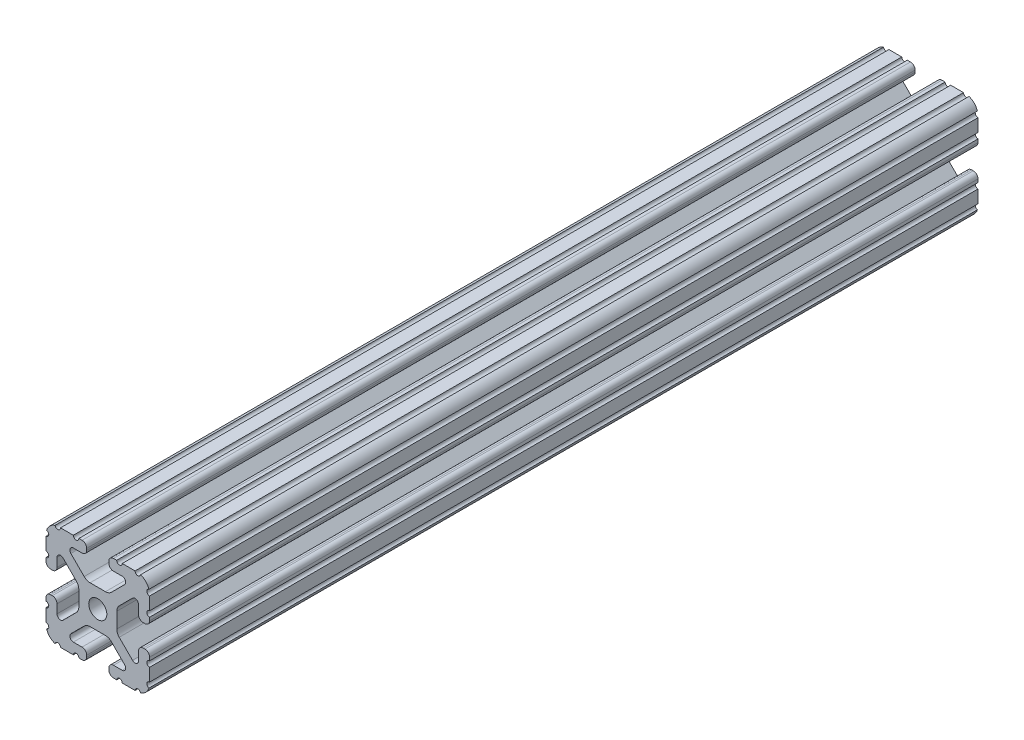
SolidWorks part; units mm, degrees
ref_plane "Front Plane" through (0, 0, 0) normal (0, 0, 1) x (1, 0, 0)
ref_plane "Top Plane" through (0, 0, 0) normal (0, 1, 0) x (1, 0, 0)
ref_plane "Right Plane" through (0, 0, 0) normal (1, 0, 0) x (0, 0, -1)
sketch "Sketch2" plane through (0, 0, 0) normal (0, 0, 1) x (1, 0, 0)
  line L0 (0, 19.05) -> (0, -19.05) construction
  line L1 (-19.05, 0) -> (19.05, 0) construction
  line L2 (4.064, -19.05) -> (19.05, -19.05)
  line L3 (19.05, -19.05) -> (19.05, -4.064)
  line L4 (4.064, -19.05) -> (4.064, -14.986)
  line L5 (4.064, -14.986) -> (12.1123, -14.986)
  line L6 (12.1123, -14.986) -> (4.1113, -6.985)
  line L7 (0, 0) -> (19.05, -19.05) construction
  line L8 (19.05, -4.064) -> (14.986, -4.064)
  line L9 (14.986, -4.064) -> (14.986, -12.1123)
  line L10 (14.986, -12.1123) -> (6.985, -4.1113)
  circle A0 centre (0, 0) radius 3.3274
  arc A1 (8.9963, -14.986) -> (9.909, -12.7826) centre (8.9963, -13.6953) ccw construction
  point P8 (0, -6.985)
  dimension "Center Hole Diameter" = 6.6548
  dimension "Rail Height" = 38.1
  dimension "Rail Width" = 38.1
  dimension "T-Slot Width" = 8.128
  dimension "Slot Inner Width" = 20.574
  dimension "Thickness" = 4.064
  dimension "Slot Depth" = 8.001
  dimension "D1" = 4.064
sketch "Sketch3" plane through (0, 0, 0) normal (1, 0, 0) x (0, 0, -1)
  line L0 (-152.4, -19.05) -> (152.4, -19.05) construction
  line L1 (-127, 0) -> (127, 0) construction
  dimension "Length" = 304.8
  dimension "D1" = 25.4
sketch "Sketch4" plane through (0, 0, 0) normal (0, 0, 1) x (1, 0, 0)
  line L0 (5.7912, -19.05) -> (14.3002, -19.05)
  line L1 (4.064, -19.05) -> (19.05, -19.05) construction
  line L2 (4.064, -19.05) -> (4.064, -14.986) construction
  line L3 (4.064, -14.986) -> (12.1123, -14.986) construction
  line L4 (4.064, -16.7132) -> (4.064, -17.3228)
  line L5 (5.7912, -14.986) -> (8.9963, -14.986)
  line L6 (0, -6.985) -> (2.833, -6.985)
  line L7 (12.1123, -14.986) -> (4.1113, -6.985) construction
  line L8 (5.0152, -7.8889) -> (9.909, -12.7826)
  line L9 (19.05, -19.05) -> (19.05, -4.064) construction
  line L10 (14.986, -12.1123) -> (6.985, -4.1113) construction
  line L11 (14.986, -4.064) -> (14.986, -12.1123) construction
  line L12 (14.986, -8.9963) -> (14.986, -5.7912)
  line L13 (19.05, -4.064) -> (14.986, -4.064) construction
  line L14 (16.7132, -4.064) -> (17.3228, -4.064)
  line L15 (19.05, -5.7912) -> (19.05, -14.3002)
  line L16 (12.7826, -9.909) -> (7.8889, -5.0152)
  line L17 (6.985, 0) -> (6.985, -2.833)
  line L18 (-19.05, 0) -> (19.05, 0) construction
  line L19 (0, -6.985) -> (0, -3.3274)
  line L20 (0, 19.05) -> (0, -19.05) construction
  line L21 (6.985, 0) -> (3.3274, 0)
  arc A0 (4.064, -17.3228) -> (5.7912, -19.05) centre (5.7912, -17.3228) ccw
  arc A2 (4.064, -16.7132) -> (5.7912, -14.986) centre (5.7912, -16.7132) cw
  arc A3 (8.9963, -14.986) -> (9.909, -12.7826) centre (8.9963, -13.6953) ccw
  arc A4 (2.833, -6.985) -> (5.0152, -7.8889) centre (2.833, -10.0711) cw
  arc A5 (14.3002, -19.05) -> (19.05, -14.3002) centre (14.3002, -14.3002) ccw
  arc A6 (12.7826, -9.909) -> (14.986, -8.9963) centre (13.6953, -8.9963) ccw
  arc A7 (14.986, -5.7912) -> (16.7132, -4.064) centre (16.7132, -5.7912) cw
  arc A8 (17.3228, -4.064) -> (19.05, -5.7912) centre (17.3228, -5.7912) cw
  arc A9 (7.8889, -5.0152) -> (6.985, -2.833) centre (10.0711, -2.833) cw
  circle A10 centre (0, 0) radius 3.3274 construction
  arc A11 (0, -3.3274) -> (3.3274, 0) centre (0, 0) ccw
  dimension "D1" = 4.7498
  dimension "D2" = 3.0861
  dimension "D3" = 1.7272
extrude "Boss-Extrude1" add sketch "Sketch4" along normal mid plane 304.8
sketch "Sketch5" plane through (0, 0, 0) normal (0, 0, 1) x (1, 0, 0)
  line L0 (4.064, -19.05) -> (19.05, -19.05) construction
  line L1 (5.7912, -14.986) -> (8.9963, -14.986) construction
  line L3 (0, 0) -> (19.05, -19.05) construction
  line L4 (8.9963, -14.986) -> (8.9963, -19.05) construction
  line L5 (12.1123, -14.986) -> (4.1113, -6.985) construction
  circle A0 centre (14.7395, -19.05) radius 1.016
  circle A1 centre (7.9803, -19.05) radius 1.016
  circle A2 centre (19.05, -14.7395) radius 1.016
  circle A3 centre (19.05, -7.9803) radius 1.016
  point P10 (7.3938, -14.986)
  point P12 (13.6953, -8.9963)
  dimension "D1" = 2.032
extrude "Cut-Extrude1" cut sketch "Sketch5" against normal through all both and the other way through all
mirror "Mirror1" about plane through (0, 0, 0) normal (1, 0, 0) of bodies 137 134
mirror "Mirror2" about plane through (0, 0, 0) normal (0, 1, 0) of bodies 135
equation "\"D1@Boss-Extrude1\"=\"Length@Sketch3\""
equation "\"D1@Sketch2\"=\"Thickness@Sketch2\""
equation "\"D2@Sketch4\"=\"Slot Inner Width@Sketch2\"*0.15"
equation "\"D1@Sketch4\"=\"D3@Sketch4\"*2.75"
equation "\"D3@Sketch4\"=\"Thickness@Sketch2\"*0.425"
equation "\"D1@Sketch5\"=\"Thickness@Sketch2\"*0.5"
